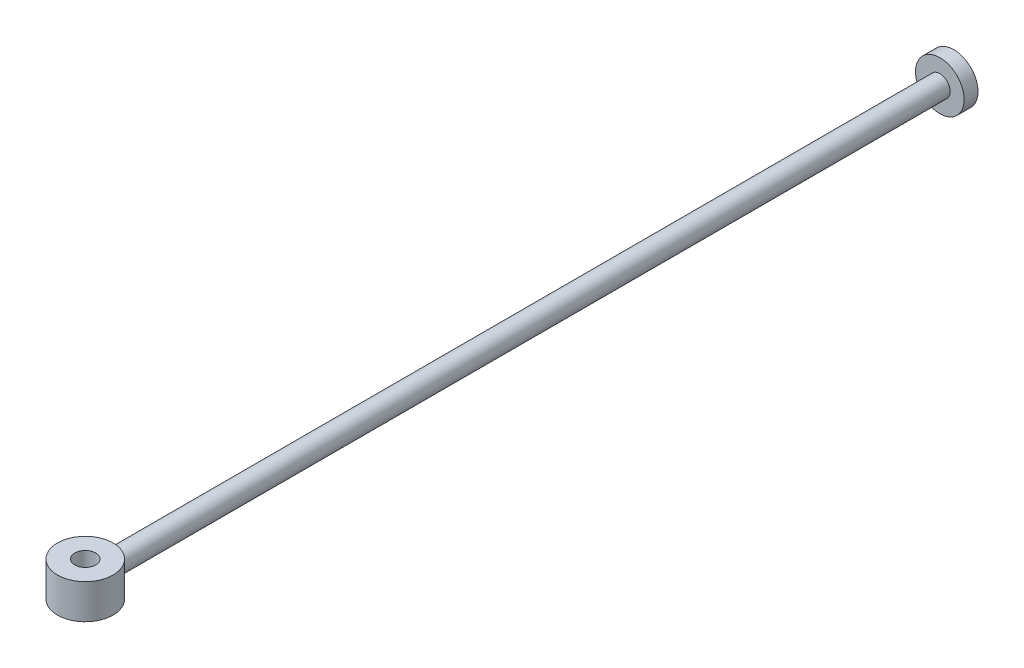
SolidWorks part; units mm, degrees
ref_plane "Front Plane" through (0, 0, 0) normal (0, 0, 1) x (1, 0, 0)
ref_plane "Top Plane" through (0, 0, 0) normal (0, 1, 0) x (1, 0, 0)
ref_plane "Right Plane" through (0, 0, 0) normal (1, 0, 0) x (0, 0, -1)
sketch "Sketch1" plane through (0, 0, 0) normal (0, 0, 1) x (1, 0, 0)
  circle A0 centre (0, 0) radius 1.5
  dimension "D1" = 3
extrude "Boss-Extrude1" add sketch "Sketch1" along normal blind 121
sketch "Sketch2" plane through (0, 0, 0) normal (0, 1, 0) x (1, 0, 0)
  line L0 (0, -121) -> (0, -125) construction
  line L1 (-1.5, -121) -> (1.5, -121) construction
  circle A0 centre (0, -125) radius 1.5
  circle A1 centre (0, -125) radius 4
  dimension "D1" = 8
  dimension "D2" = 3
extrude "Boss-Extrude2" add sketch "Sketch2" along normal blind 2.5 and the other way blind 2.5
sketch "Sketch3" plane through (0, 0, 0) normal (0, 0, -1) x (-1, 0, 0)
  circle A0 centre (0, 0) radius 3.5
  circle A1 centre (0, 0) radius 1.5 construction
  dimension "D1" = 2
extrude "Boss-Extrude3" add sketch "Sketch3" against normal blind 2
